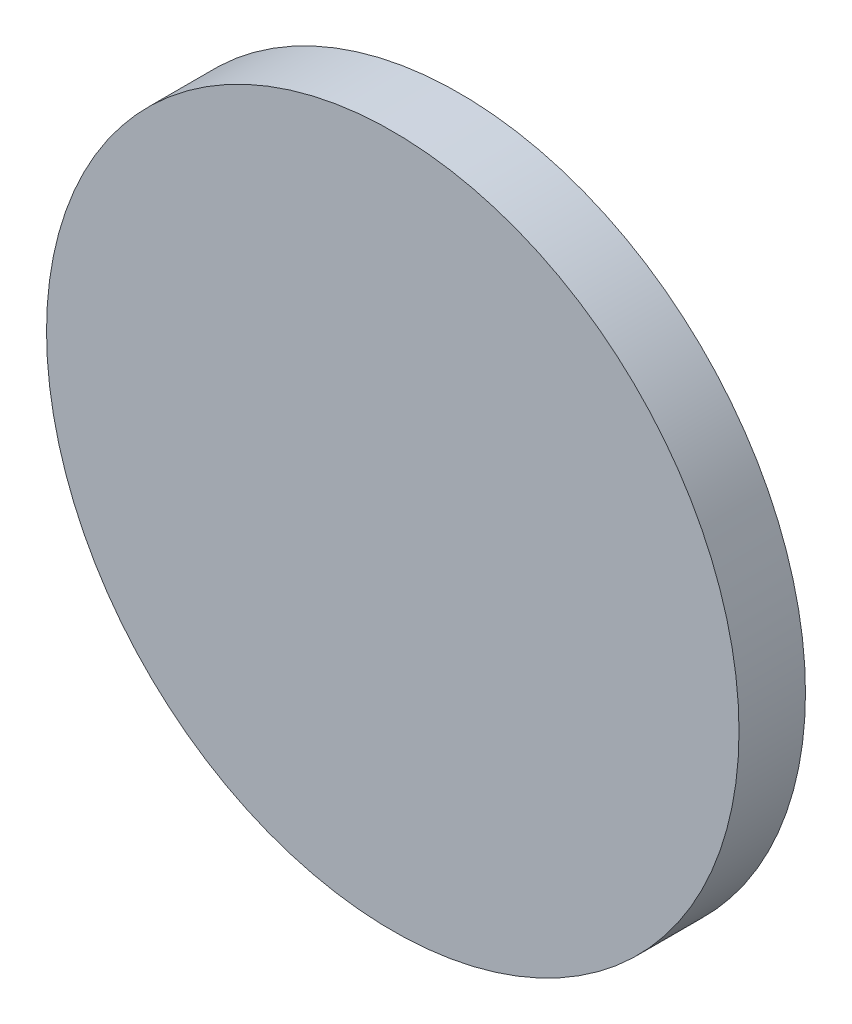
SolidWorks part; units mm, degrees
ref_plane "Front Plane" through (0, 0, 0) normal (0, 0, 1) x (1, 0, 0)
ref_plane "Top Plane" through (0, 0, 0) normal (0, 1, 0) x (1, 0, 0)
ref_plane "Right Plane" through (0, 0, 0) normal (1, 0, 0) x (0, 0, -1)
sketch "Sketch1" plane through (0, 0, 0) normal (0, 0, 1) x (1, 0, 0)
  circle A0 centre (0, 0) radius 52.1051
extrude "Boss-Extrude1" add sketch "Sketch1" along normal blind 10
